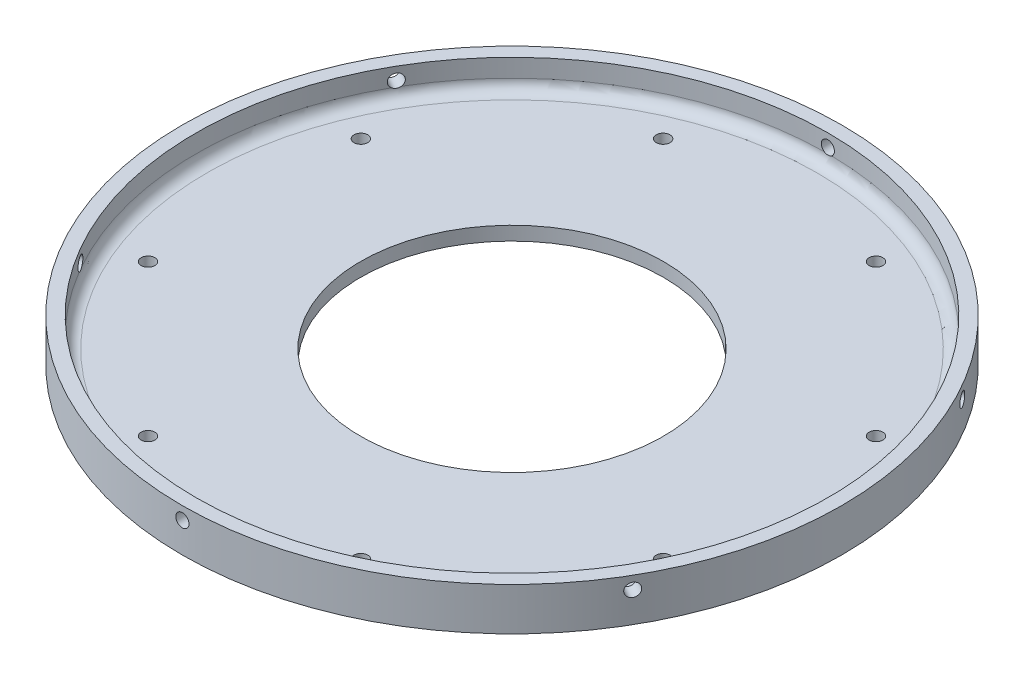
SolidWorks part; units mm, degrees
material "6061-T6 (SS)"
ref_plane "Front Plane" through (0, 0, 0) normal (0, 0, 1) x (1, 0, 0)
ref_plane "Top Plane" through (0, 0, 0) normal (0, 1, 0) x (1, 0, 0)
ref_plane "Right Plane" through (0, 0, 0) normal (1, 0, 0) x (0, 0, -1)
sketch "Sketch5" plane through (0, 0, 0) normal (0, 0, 1) x (1, 0, 0)
  line L0 (0, -81.0912) -> (0, 91.6745) construction
  line L1 (-176.4413, 0) -> (90.7126, 0) construction
  line L2 (-35, 0) -> (-76.2, 0)
  line L3 (-35, 0) -> (-35, 3.175)
  line L4 (-35, 3.175) -> (-73.025, 3.175)
  line L7 (-76.2, 0) -> (-76.2, 9.9)
  line L8 (-76.2, 9.9) -> (-73.025, 9.9)
  line L9 (-73.025, 3.175) -> (-73.025, 9.9)
  dimension "D1" = 41.2
  dimension "D2" = 3.175
  dimension "D3" = 9.9
  dimension "D4" = 3.175
  dimension "D6" = 35
revolve "Revolve1" add sketch "Sketch5" angle 360 about L0
fillet "Fillet1" radius 2.54 1 edges at (0, 3.175, -73.025)
sketch "Sketch7" plane through (0, 0, 0) normal (0, 0, 1) x (1, 0, 0)
  circle A0 centre (0.0103, 6.985) radius 0.6
  dimension "D1" = 6.985
hole_wizard "#31 (0.12) Diameter Hole1" positions "Sketch9" profile "Sketch10" hole size "#31" standard "ANSI Inch" end condition through all
sketch "Sketch9" plane through (0, 0, 0) normal (0, 0, 1) x (1, 0, 0)
  point P0 (0.0103, 6.985)
sketch "Sketch10" plane through (0.0103, 6.985, 0) normal (1, 0, 0) x (0, 1, 0)
  line L0 (0, 0) -> (0, 104.0911)
  line L1 (0, 104.0911) -> (1.524, 104.0911)
  line L2 (1.524, 104.0911) -> (1.524, 0)
  line L5 (1.524, 0) -> (0, 0)
  line L11 (0, -6.35) -> (0, 107.95) construction
  dimension "Thru Hole Dia." = 3.048
  dimension "Thru Hole Depth" = 104.0911
pattern_circular "CirPattern1" count 6 over 360 about axis through (0, -81.0912, 0) along (0, -1, 0) of "#31 (0.12) Diameter Hole1"
sketch "Sketch11" plane through (0, 3.175, 0) normal (0, 1, 0) x (1, 0, 0)
  line L0 (-50, 50) -> (50, 50) construction
  line L1 (-50, 50) -> (-50, -50) construction
  line L2 (-50, -50) -> (50, -50) construction
  line L3 (50, -50) -> (50, 50) construction
  line L4 (-24.6, 50) -> (-24.6, 59.525) construction
  line L5 (24.6, 50) -> (24.6, 59.525) construction
  line L6 (50, 50) -> (-50, -50) construction
  line L7 (-50, 50) -> (50, -50) construction
  line L8 (-24.6, -50) -> (-24.6, -59.525) construction
  line L9 (24.6, -50) -> (24.6, -59.525) construction
  line L10 (-50, 24.6) -> (-59.525, 24.6) construction
  line L11 (-50, -24.6) -> (-59.525, -24.6) construction
  line L12 (50, 24.6) -> (59.525, 24.6) construction
  line L13 (50, -24.6) -> (59.525, -24.6) construction
  dimension "D1" = 25.4
  dimension "D2" = 25.4
  dimension "D3" = 9.525
  dimension "D4" = 9.525
  dimension "D5" = 100
  dimension "D6" = 25.4
  dimension "D7" = 25.4
  dimension "D8" = 9.525
  dimension "D9" = 9.525
  dimension "D10" = 9.525
  dimension "D11" = 9.525
hole_wizard "1/8 (0.125) Diameter Hole1" positions "Sketch16" profile "Sketch15" hole size "1/8" standard "ANSI Inch" end condition through all
sketch "Sketch16" plane through (0, 0, 0) normal (0, 1, 0) x (1, 0, 0)
  point P0 (-24.6, 59.525)
  point P3 (24.6, 59.525)
  point P6 (-59.525, 24.6)
  point P9 (-59.525, -24.6)
  point P12 (-24.6, -59.525)
  point P15 (24.6, -59.525)
  point P18 (59.525, -24.6)
  point P21 (59.525, 24.6)
sketch "Sketch15" plane through (-24.6, 0, -59.525) normal (1, 0, 0) x (0, 0, -1)
  line L0 (0, 0) -> (0, 9.9)
  line L1 (0, 9.9) -> (1.5875, 9.9)
  line L2 (1.5875, 9.9) -> (1.5875, 0)
  line L5 (1.5875, 0) -> (0, 0)
  line L11 (0, -6.35) -> (0, 107.95) construction
  dimension "Thru Hole Dia." = 3.175
  dimension "Thru Hole Depth" = 9.9
